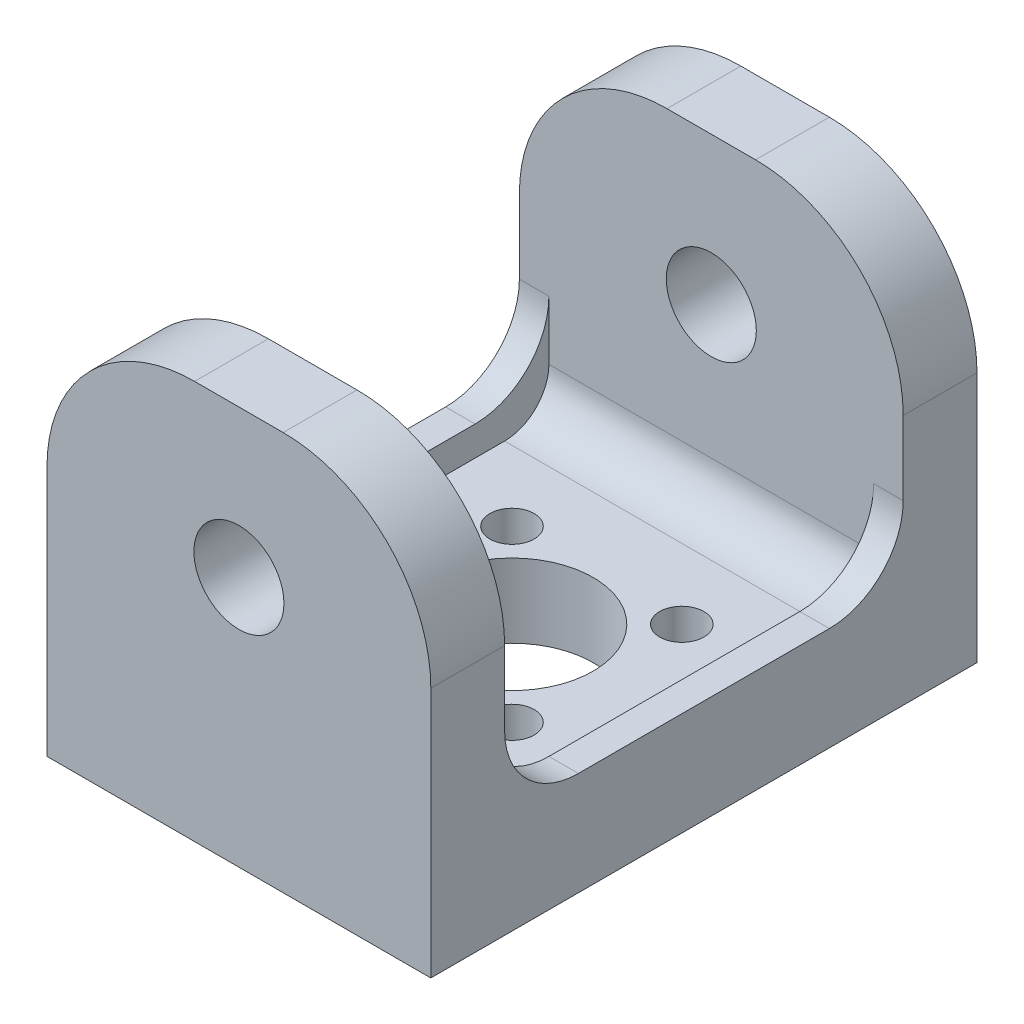
SolidWorks part; units mm, degrees
ref_plane "Front Plane" through (0, 0, 0) normal (0, 0, 1) x (1, 0, 0)
ref_plane "Top Plane" through (0, 0, 0) normal (0, 1, 0) x (1, 0, 0)
ref_plane "Right Plane" through (0, 0, 0) normal (1, 0, 0) x (0, 0, -1)
sketch "Sketch1" plane through (0, 0, 0) normal (0, 1, 0) x (1, 0, 0)
  line L1 (-13, 18.5) -> (13, 18.5)
  line L2 (-13, 18.5) -> (-13, -18.5)
  line L3 (-13, -18.5) -> (13, -18.5)
  line L4 (13, 18.5) -> (13, -18.5)
  line L5 (-13, 18.5) -> (13, -18.5) construction
  line L6 (-13, -18.5) -> (13, 18.5) construction
  point P0 (0, 0)
  dimension "D1" = 26
  dimension "D2" = 37
extrude "Boss-Extrude1" add sketch "Sketch1" along normal blind 5
sketch "Sketch2" plane through (0, 0, 0) normal (0, 1, 0) x (1, 0, 0)
  circle A0 centre (-5.75, 5.75) radius 1.5
  circle A1 centre (0, 0) radius 5.5
  circle A2 centre (5.75, 5.75) radius 1.5
  circle A3 centre (5.75, -5.75) radius 1.5
  circle A4 centre (-5.75, -5.75) radius 1.5
  point P14 (0, 0)
  dimension "D1" = 3
  dimension "D3" = 5.75
  dimension "D4" = 11
  dimension "D2" = 5.75
  dimension "D5" = 4
extrude "Cut-Extrude1" cut sketch "Sketch2" along normal through all
sketch "Sketch3" plane through (0, 0, 0) normal (0, 1, 0) x (1, 0, 0)
  line L0 (13, -18.5) -> (13, 18.5) construction
  line L1 (-13, 18.5) -> (13, 18.5)
  line L2 (-13, 18.5) -> (-13, 13.5)
  line L3 (-13, 13.5) -> (13, 13.5)
  line L4 (13, 18.5) -> (13, 13.5)
  line L5 (-14.3, 0) -> (14.3, 0) construction
  line L6 (13, -18.5) -> (13, -13.5)
  line L7 (-13, -13.5) -> (13, -13.5)
  line L8 (-13, -18.5) -> (-13, -13.5)
  line L9 (-13, -18.5) -> (13, -18.5)
  dimension "D1" = 5
extrude "Boss-Extrude2" add sketch "Sketch3" along normal blind 27
sketch "Sketch4" plane through (0, 0, 0) normal (0, 0, 1) x (1, 0, 0)
  circle A0 centre (0, 17) radius 3.05
  dimension "D1" = 6.1
  dimension "D2" = 17
extrude "Cut-Extrude2" cut sketch "Sketch4" against normal through all both and the other way through all contours A0
fillet "Fillet1" radius 10 4 edges at (-13, 27, -16) (-13, 27, 16) (13, 27, 16) (13, 27, -16)
fillet "Fillet2" radius 3 2 edges at (0, 5, 13.5) (0, 5, -13.5)
sketch "Sketch5" plane through (0, 0, 0) normal (0, 1, 0) x (1, 0, 0)
  line L0 (-13, -18.5) -> (-3, -18.5) construction
  line L1 (-13, 18.5) -> (-11, 18.5)
  line L2 (-13, 18.5) -> (-13, -18.5)
  line L3 (-13, -18.5) -> (-11, -18.5)
  line L4 (-11, 18.5) -> (-11, -18.5)
  line L5 (0, -14.85) -> (0, 14.85) construction
  line L6 (11, 18.5) -> (11, -18.5)
  line L7 (13, -18.5) -> (11, -18.5)
  line L8 (13, 18.5) -> (13, -18.5)
  line L9 (13, 18.5) -> (11, 18.5)
  dimension "D1" = 2
extrude "Boss-Extrude3" add sketch "Sketch5" along normal blind 7
fillet "Fillet3" radius 5 4 edges at (12, 7, -13.3284) (12, 7, 13.3284) (-12, 7, 13.3284) (-12, 7, -13.3284)
